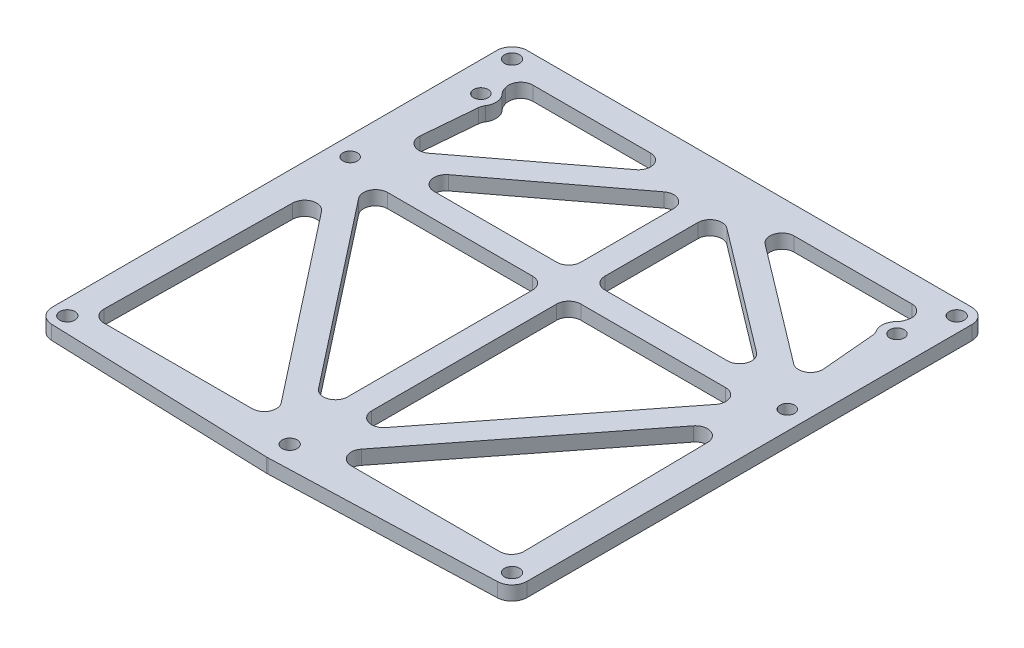
SolidWorks part; units mm, degrees
ref_plane "Front Plane" through (0, 0, 0) normal (0, 0, 1) x (1, 0, 0)
ref_plane "Top Plane" through (0, 0, 0) normal (0, 1, 0) x (1, 0, 0)
ref_plane "Right Plane" through (0, 0, 0) normal (1, 0, 0) x (0, 0, -1)
sketch "Sketch1" plane through (0, 0, 0) normal (0, 1, 0) x (1, 0, 0)
  line L0 (-43.8131, 37.2517) -> (-46.0269, 11.9483) construction
  line L1 (-50, -50) -> (50, -50) construction
  line L2 (-50, -50) -> (-50, 50) construction
  line L3 (-50, 50) -> (50, 50) construction
  line L4 (50, -50) -> (50, 50) construction
  line L5 (-50, -50) -> (50, 50) construction
  line L6 (-50, 50) -> (50, -50) construction
  line L7 (-46.0269, 11.9483) -> (-46.0269, 36.2261) construction
  line L8 (0, 0) -> (0, 21.5211) construction
  circle A0 centre (-46.825, -46.825) radius 1.5875
  circle A1 centre (-46.825, 46.825) radius 1.5875
  circle A2 centre (46.825, 46.825) radius 1.5875
  circle A3 centre (46.825, -46.825) radius 1.5875
  circle A4 centre (-43.8131, 37.2517) radius 1.524
  circle A5 centre (-46.0269, 11.9483) radius 1.524
  circle A6 centre (46.0269, 11.9483) radius 1.524
  circle A7 centre (43.8131, 37.2517) radius 1.524
  circle A8 centre (0, -46.825) radius 1.5875
  point P0 (0, 0)
  point P17 (0, 0)
  point P20 (-44.92, 24.6)
  dimension "D3" = 3.175
  dimension "D4" = 3.175
  dimension "D8" = 3.048
  dimension "D11" = 3.175
  dimension "D12" = 3.175
  dimension "D1" = 100
  dimension "D2" = 100
  dimension "D6" = 5
  dimension "D7" = 25.4
  dimension "D9" = 5.08
  dimension "D10" = 25.4
  dimension "D5" = 4
sketch "Sketch2" plane through (0, 0, 0) normal (0, 1, 0) x (1, 0, 0)
  line L0 (0.1615, -51.5848) -> (46.9326, -49.9982)
  line L1 (-0.1615, -51.5848) -> (-46.9326, -49.9982)
  line L2 (-46.825, 50) -> (46.825, 50)
  line L3 (50, 46.825) -> (50, -46.825)
  line L4 (-50, -46.825) -> (-50, 46.825)
  circle A0 centre (46.825, 46.825) radius 1.5875 construction
  circle A1 centre (43.8131, 37.2517) radius 1.524 construction
  circle A2 centre (46.0269, 11.9483) radius 1.524 construction
  circle A3 centre (46.825, -46.825) radius 1.5875 construction
  circle A4 centre (0, -46.825) radius 1.5875 construction
  circle A5 centre (-46.825, -46.825) radius 1.5875 construction
  circle A6 centre (-46.0269, 11.9483) radius 1.524 construction
  circle A7 centre (-43.8131, 37.2517) radius 1.524 construction
  circle A8 centre (-46.825, 46.825) radius 1.5875 construction
  circle A9 centre (46.825, 46.825) radius 1.5875
  circle A10 centre (43.8131, 37.2517) radius 1.524
  circle A11 centre (46.0269, 11.9483) radius 1.524
  circle A12 centre (46.825, -46.825) radius 1.5875
  circle A13 centre (0, -46.825) radius 1.5875
  circle A14 centre (-46.825, -46.825) radius 1.5875
  circle A15 centre (-46.0269, 11.9483) radius 1.524
  circle A16 centre (-43.8131, 37.2517) radius 1.524
  circle A17 centre (-46.825, 46.825) radius 1.5875
  circle A18 centre (-46.825, 46.825) radius 3.175
  circle A19 centre (-43.8131, 37.2517) radius 3.175
  circle A20 centre (-46.0269, 11.9483) radius 3.175
  circle A21 centre (-46.825, -46.825) radius 3.175
  circle A23 centre (46.825, -46.825) radius 3.175
  circle A24 centre (46.0269, 11.9483) radius 3.175
  circle A25 centre (43.8131, 37.2517) radius 3.175
  circle A26 centre (46.825, 46.825) radius 3.175
  circle A27 centre (0, -46.825) radius 4.7625
  dimension "D1" = 6.35
  dimension "D2" = 9.525
extrude "Boss-Extrude2" add sketch "Sketch2" along normal blind 2.9718 contours A27 L0 A23 L3 A26 L2 A18 L4 A21 L1 A19 A20 A24 A25 | A21 A14 | A27 A13 | A23 A12 | A24 A11 | A25 A10 | A26 A9 | A19 A16 | A18 A17 | A20 A15 region at (0, 0, 0.3641) region at (0, 0, 51.4528) region at (44.6068, 0, 44.6807) region at (-49.0432, 0, 48.9693) region at (44.6434, 0, -44.6434) region at (-49.0066, 0, -49.0066) region at (-46.8983, 0, -37.2517) region at (-49.1121, 0, -11.9483) region at (42.9417, 0, -11.9483) region at (40.7279, 0, -37.2517)
sketch "Sketch3" plane through (0, 0, 0) normal (0, 1, 0) x (1, 0, 0)
  line L0 (-46.825, -46.825) -> (0, -46.825) construction
  line L1 (0, -46.825) -> (46.825, -46.825) construction
  line L2 (46.825, -46.825) -> (46.0269, 11.9483) construction
  line L3 (46.0269, 11.9483) -> (46.825, 46.825) construction
  line L4 (46.825, 46.825) -> (-46.825, 46.825) construction
  line L5 (-46.825, 46.825) -> (-46.0269, 11.9483) construction
  line L6 (-46.0269, 11.9483) -> (-46.825, -46.825) construction
  line L7 (0, -46.825) -> (-46.0269, 11.9483) construction
  line L8 (-46.0269, 11.9483) -> (46.0269, 11.9483) construction
  line L9 (46.0269, 11.9483) -> (0, -46.825) construction
  line L10 (43.8131, 37.2517) -> (46.825, 46.825) construction
  line L11 (-46.825, 46.825) -> (-43.8131, 37.2517) construction
  line L12 (46.0269, 11.9483) -> (0, 46.825) construction
  line L13 (0, 46.825) -> (-46.0269, 11.9483) construction
  line L14 (43.8131, 37.2517) -> (46.0269, 11.9483) construction
  line L15 (-46.0269, 11.9483) -> (-43.8131, 37.2517) construction
  line L16 (0, 11.9483) -> (0, -46.825) construction
  line L17 (0, 46.825) -> (0, 11.9483) construction
  line L18 (46.825, 49.365) -> (-46.825, 49.365)
  line L19 (-2.54, 46.825) -> (-2.54, 11.9483)
  line L20 (47.5609, 13.9728) -> (0, 50.0118)
  line L21 (0, 50.0118) -> (-47.5609, 13.9728)
  line L22 (-46.0269, 9.4083) -> (46.0269, 9.4083)
  line L23 (1.9998, -45.2589) -> (-44.0271, 13.5144)
  line L24 (-2.54, 11.9483) -> (-2.54, -46.825)
  line L25 (44.0271, 13.5144) -> (-1.9998, -45.2589)
  line L26 (0, -49.365) -> (49.3997, -49.365)
  line L27 (49.3997, -49.365) -> (48.5666, 11.9828)
  line L28 (-48.5666, 11.9828) -> (-49.3997, -49.365)
  line L29 (-49.3997, -49.365) -> (0, -49.365)
  line L30 (41.2828, 37.0303) -> (43.4965, 11.727)
  line L31 (48.5662, 11.8902) -> (49.3643, 46.7669)
  line L32 (46.236, 36.4894) -> (49.2479, 46.0627)
  line L33 (-49.2479, 46.0627) -> (-46.236, 36.4894)
  line L34 (-49.3643, 46.7669) -> (-48.5662, 11.8902)
  line L35 (-43.4965, 11.727) -> (-41.2828, 37.0303)
  line L36 (46.825, 44.285) -> (-46.825, 44.285)
  line L37 (2.54, 46.825) -> (2.54, 11.9483)
  line L38 (44.4929, 9.9239) -> (0, 43.6382)
  line L39 (0, 43.6382) -> (-44.4929, 9.9239)
  line L40 (-46.0269, 14.4883) -> (46.0269, 14.4883)
  line L41 (-1.9998, -48.3911) -> (-48.0266, 10.3823)
  line L42 (2.54, 11.9483) -> (2.54, -46.825)
  line L43 (48.0266, 10.3823) -> (1.9998, -48.3911)
  line L44 (0, -44.285) -> (44.2503, -44.285)
  line L45 (44.2503, -44.285) -> (43.4871, 11.9138)
  line L46 (-43.4871, 11.9138) -> (-44.2503, -44.285)
  line L47 (-44.2503, -44.285) -> (0, -44.285)
  line L48 (46.3435, 37.473) -> (48.5572, 12.1697)
  line L49 (43.4875, 12.0064) -> (44.2857, 46.8831)
  line L50 (41.3902, 38.014) -> (44.4021, 47.5873)
  line L51 (-44.4021, 47.5873) -> (-41.3902, 38.014)
  line L52 (-44.2857, 46.8831) -> (-43.4875, 12.0064)
  line L53 (-48.5572, 12.1697) -> (-46.3435, 37.473)
  circle A0 centre (-46.0269, 11.9483) radius 3.175 construction
  circle A1 centre (-43.8131, 37.2517) radius 3.175 construction
  circle A2 centre (-46.825, 46.825) radius 3.175 construction
  circle A3 centre (46.825, 46.825) radius 3.175 construction
  circle A4 centre (43.8131, 37.2517) radius 3.175 construction
  circle A5 centre (46.0269, 11.9483) radius 3.175 construction
  circle A6 centre (46.825, -46.825) radius 3.175 construction
  circle A7 centre (0, -46.825) radius 4.7625 construction
  circle A8 centre (-46.825, -46.825) radius 3.175 construction
  circle A9 centre (-46.0269, 11.9483) radius 3.175
  circle A10 centre (-43.8131, 37.2517) radius 3.175
  circle A11 centre (-46.825, 46.825) radius 3.175
  circle A12 centre (46.825, 46.825) radius 3.175
  circle A13 centre (43.8131, 37.2517) radius 3.175
  circle A14 centre (46.0269, 11.9483) radius 3.175
  circle A15 centre (46.825, -46.825) radius 3.175
  circle A16 centre (0, -46.825) radius 4.7625
  circle A17 centre (-46.825, -46.825) radius 3.175
  dimension "D1" = 2.54
  dimension "D2" = 2.54
  dimension "D3" = 2.54
  dimension "D4" = 2.54
extrude "Cut-Extrude1" cut sketch "Sketch3" along normal through all contours L46 L47 L41 | L24 L22 L23 | L22 L42 L25 | L44 L45 L43 | A13 L50 L36 L20 L30 | L37 L40 L38 | L39 L40 L19 | A10 L35 L21 L36 L51 region at (30.5759, 0, -35.4582) region at (-30.5759, 0, -35.4582) region at (14.5164, 0, -23.5634) region at (-14.5164, 0, -23.5634) region at (15.2972, 0, 6.8818) region at (31.0168, 0, 27.9532) region at (-31.0168, 0, 27.9532) region at (-15.2972, 0, 6.8818)
fillet "Fillet1" radius 2.54 28 edges at (-5.2153, 1.4859, 44.285) (-43.5849, 1.4859, -4.7105) (-44.2503, 1.4859, 44.285) (43.5849, 1.4859, -4.7105) (5.2153, 1.4859, 44.285) (44.2503, 1.4859, 44.285) (2.54, 1.4859, -9.4083) (2.54, 1.4859, 39.462) (40.8116, 1.4859, -9.4083) (-40.8116, 1.4859, -9.4083) (-2.54, 1.4859, 39.462) (-43.3631, 1.4859, -44.285) (-41.9619, 1.4859, -39.8311) (41.9619, 1.4859, -39.8311) (43.3631, 1.4859, -44.285) (-2.54, 1.4859, -9.4083) (-2.54, 1.4859, -14.4883) (-2.54, 1.4859, -41.7135) (-38.4691, 1.4859, -14.4883) (38.4691, 1.4859, -14.4883) (2.54, 1.4859, -41.7135) (2.54, 1.4859, -14.4883) (-41.4488, 1.4859, -35.1325) (-42.9975, 1.4859, -17.4306) (-7.5577, 1.4859, -44.285) (7.5577, 1.4859, -44.285) (42.9975, 1.4859, -17.4306) (41.4488, 1.4859, -35.1325)
